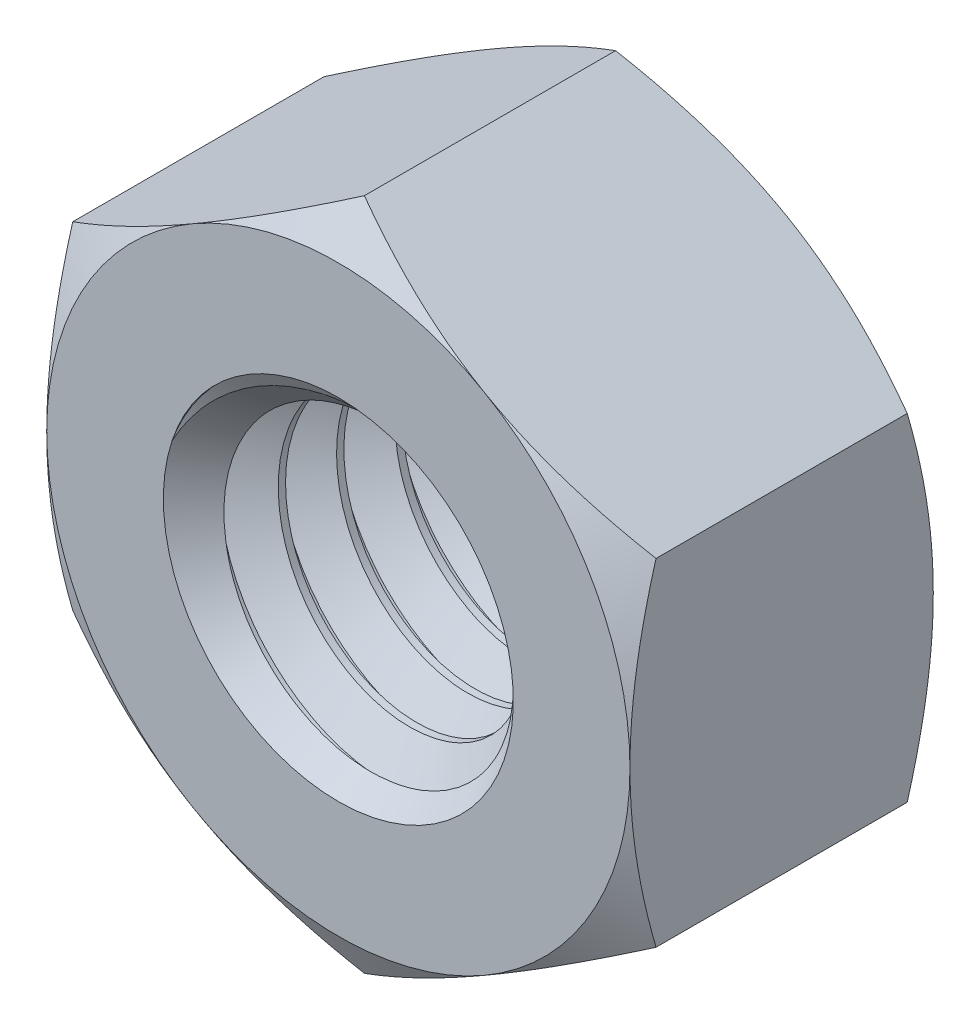
SolidWorks part; units mm, degrees
note: '?' marks a value the reader was unsure of.
ref_plane "Front" through (0, 0, 0) normal (0, 0, 1) x (1, 0, 0)
ref_plane "Top" through (0, 0, 0) normal (0, 1, 0) x (1, 0, 0)
ref_plane "Right" through (0, 0, 0) normal (1, 0, 0) x (0, 0, -1)
sketch "Sketch1" plane through (0, 0, 0) normal (0, 0, 1) x (1, 0, 0)
  line L1 (-5, 2.8868) -> (-5, -2.8868)
  line L2 (-5, -2.8868) -> (0, -5.7735)
  line L3 (0, -5.7735) -> (5, -2.8868)
  line L4 (5, -2.8868) -> (5, 2.8868)
  line L5 (5, 2.8868) -> (0, 5.7735)
  line L6 (0, 5.7735) -> (-5, 2.8868)
  circle A0 centre (0, 0) radius 5 construction
  circle A1 centre (0, 0) radius 3 construction
  point P10 (0, 3)
  dimension "hex" = 10
  dimension "dia" = 6
extrude "Extrude1" add sketch "Sketch1" along normal mid plane 5.2
sketch "Sketch4" plane through (0, 0, -2.6) normal (0, 0, -1) x (-1, 0, 0)
  circle A0 centre (0, 0) radius 3 construction
  circle A1 centre (0, 0) radius 3
sketch "Sketch10" plane through (0, 0, 2.6) normal (0, 0, 1) x (1, 0, 0)
  circle A0 centre (0, 0) radius 3 construction
  circle A1 centre (0, 0) radius 3
extrude "Cut-Extrude2" cut sketch "Sketch10" against normal through all draft 45
sketch "Sketch11" plane through (0, 0, -2.6) normal (0, 0, -1) x (-1, 0, 0)
  circle A0 centre (0, 0) radius 3 construction
  circle A1 centre (0, 0) radius 3
extrude "Cut-Extrude3" cut sketch "Sketch11" against normal through all draft 45
sketch "Sketch13" plane through (0, 0, -2.6) normal (0, 0, -1) x (-1, 0, 0)
  circle A0 centre (0, 0) radius 3 construction
  circle A1 centre (0, 0) radius 3
extrude "Boss-Extrude1" add sketch "Sketch13" against normal up to vertex (5.2 mm away) separate body up to point (-5, 2.8868, 2.6)
curve "Helix/Spiral3" pitch 1 height 5.2 turns 5.2
sketch "Sketch12" plane through (0, 0, 0) normal (1, 0, 0) x (0, 0, -1)
  line L0 (3.475, 3) -> (2.6, 3)
  line L1 (3.475, 3) -> (3.1, 2.3505)
  line L2 (3.1, 2.3505) -> (2.975, 2.3505)
  line L3 (2.975, 2.3505) -> (2.6, 3)
  line L4 (3.0375, 2.3505) -> (3.0375, 3) construction
  line L5 (2.7875, 2.6752) -> (3.2875, 2.6752) construction
  dimension "D1" = 60
  dimension "D2" = 0.125
  dimension "D3" = 0.5
sweep "Cut-Sweep1" cut profiles "Sketch12" path "Helix/Spiral3"
combine bodies "Combine1" operation type subtract main body 116 bodies to subtract 118
sketch "Sketch7" plane through (0, 0, 2.6) normal (0, 0, 1) x (1, 0, 0)
  circle A0 centre (0, 0) radius 5 construction
  circle A1 centre (0, 0) radius 5
extrude "Extrude2" cut sketch "Sketch7" against normal blind 25.4 draft 60 flip side to cut
mirror "Mirror2" about plane through (0, 0, 0) normal (0, 0, 1) of "Extrude2"
sketch "Sketch8" plane through (0, 0, 2.6) normal (0, 0, 1) x (1, 0, 0)
  line L0 (-2.1213, 2.1213) -> (0, 0) construction
  line L1 (0, -2.9882) -> (0, 2.9882) construction
  circle A1 centre (0, 0) radius 3 construction
  point P0 (-2.1213, 2.1213)
  dimension "D1" = 45
sketch "Sketch14" plane through (0, 0, 2.6) normal (0, 0, 1) x (1, 0, 0)
  line L0 (0, 0) -> (-3, 0) construction
  arc A0 (0, 3) -> (-2.8514, 0.9326) centre (0, 0) ccw construction
ref_axis "Axis1" through (0, 0, -3.3005) along (0, 0, 1)?
equation "\"D3@Helix/Spiral3\" = \"length@Extrude1\" "
equation "\"D2@Sketch12\" = \"D4@Helix/Spiral3\"*.125"
equation "\"D3@Sketch12\" = \"D4@Helix/Spiral3\"*.50"
